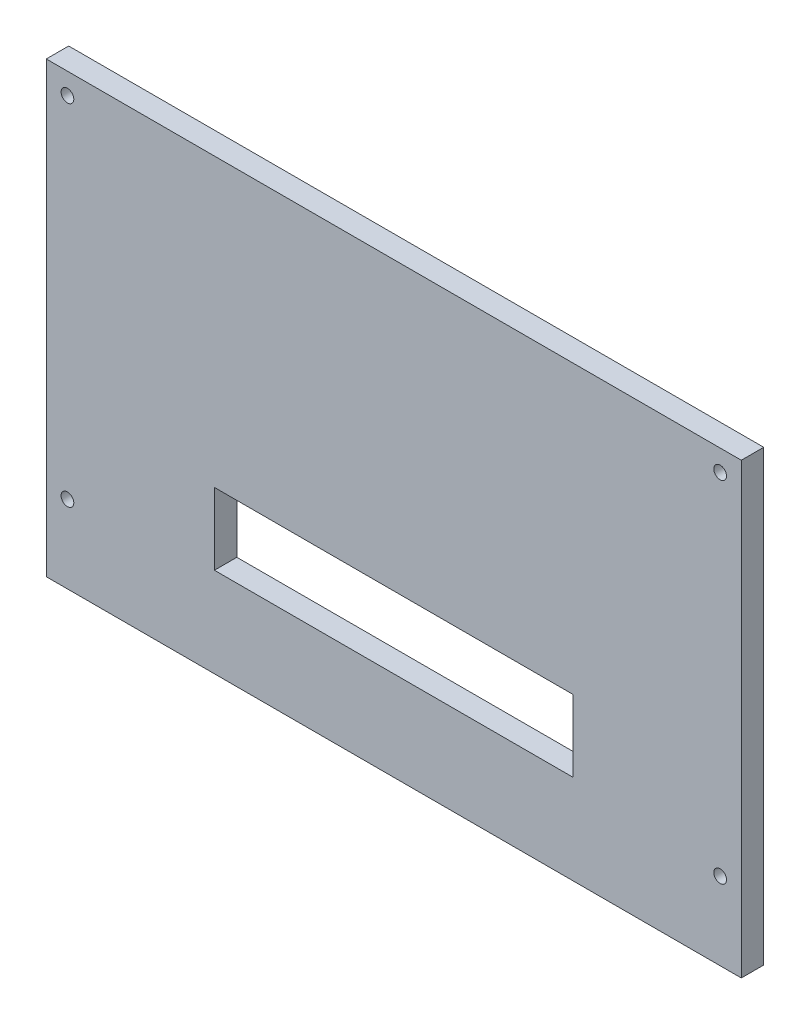
SolidWorks part; units mm, degrees
material "Acrylic (Medium-high impact)"
ref_plane "Front Plane" through (0, 0, 0) normal (0, 0, 1) x (1, 0, 0)
ref_plane "Top Plane" through (0, 0, 0) normal (0, 1, 0) x (1, 0, 0)
ref_plane "Right Plane" through (0, 0, 0) normal (1, 0, 0) x (0, 0, -1)
sketch "Sketch1" plane through (0, 0, 0) normal (0, 0, 1) x (1, 0, 0)
  line L1 (196.85, 127) -> (0, 127)
  line L2 (196.85, 127) -> (196.85, 0)
  line L3 (196.85, 0) -> (0, 0)
  line L4 (0, 127) -> (0, 0)
  line L5 (196.85, 127) -> (0, 0) construction
  line L6 (196.85, 0) -> (0, 127) construction
  point P0 (98.425, 63.5)
  dimension "D1" = 127
  dimension "D2" = 196.85
extrude "Boss-Extrude1" add sketch "Sketch1" along normal blind 6.35
hole_wizard "M3 Clearance Hole1" positions "Sketch2" profile "Sketch3" hole size "M3" standard "ANSI Metric" end condition through all
sketch "Sketch2" plane through (0, 0, 6.35) normal (0, 0, 1) x (1, 0, 0)
  line L0 (0, 127) -> (0, 0) construction
  line L1 (196.85, 127) -> (0, 127) construction
  line L2 (196.85, 0) -> (196.85, 127) construction
  line L3 (0, 0) -> (196.85, 0) construction
  point P0 (5.9944, 121.0056)
  point P2 (5.9944, 21.9964)
  point P4 (190.8556, 21.9964)
  point P6 (190.8556, 121.0056)
  dimension "D1" = 5.9944
  dimension "D2" = 5.9944
  dimension "D3" = 5.9944
  dimension "D4" = 21.9964
sketch "Sketch3" plane through (5.9944, 121.0056, 6.35) normal (1, 0, 0) x (0, -1, 0)
  line L0 (0, 0) -> (0, 6.35)
  line L1 (0, 6.35) -> (1.8, 6.35)
  line L2 (1.8, 6.35) -> (1.8, 0)
  line L5 (1.8, 0) -> (0, 0)
  line L11 (0, -6.35) -> (0, 107.95) construction
  dimension "Thru Hole Dia." = 3.6
  dimension "Thru Hole Depth" = 6.35
sketch "Sketch4" plane through (0, 0, 6.35) normal (0, 0, 1) x (1, 0, 0)
  line L0 (0, 127) -> (0, 0) construction
  line L1 (46.99, 107.95) -> (50.4952, 107.95)
  line L2 (46.99, 107.95) -> (46.99, 44.45)
  line L3 (46.99, 44.45) -> (50.4952, 44.45)
  line L4 (50.4952, 107.95) -> (50.4952, 44.45)
  line L5 (146.3548, 107.95) -> (149.86, 107.95)
  line L6 (146.3548, 107.95) -> (146.3548, 44.45)
  line L7 (146.3548, 44.45) -> (149.86, 44.45)
  line L8 (149.86, 107.95) -> (149.86, 44.45)
  line L9 (196.85, 0) -> (196.85, 127) construction
  line L10 (196.85, 127) -> (0, 127) construction
  dimension "D1" = 3.5052
  dimension "D2" = 63.5
  dimension "D3" = 46.99
  dimension "D4" = 46.99
  dimension "D5" = 19.05
extrude "Cut-Extrude1" [suppressed] cut sketch "Sketch4" against normal through all
sketch "Sketch5" plane through (0, 0, 6.35) normal (0, 0, 1) x (1, 0, 0)
  line L0 (0, 36.1092) -> (76.2, 25.4)
  line L1 (0, 127) -> (0, 0) construction
  line L2 (76.2, 25.4) -> (120.65, 25.4)
  line L3 (120.65, 25.4) -> (196.85, 36.1092)
  line L4 (196.85, 0) -> (196.85, 127) construction
  line L5 (196.85, 36.1092) -> (196.85, 0)
  line L6 (196.85, 0) -> (0, 0)
  line L7 (0, 0) -> (0, 36.1092)
  dimension "D1" = 8
  dimension "D2" = 8
  dimension "D3" = 76.2
  dimension "D4" = 76.2
  dimension "D5" = 25.4
extrude "Cut-Extrude2" [suppressed] cut sketch "Sketch5" against normal through all
sketch "Sketch7" plane through (0, 0, 6.35) normal (0, 0, 1) x (1, 0, 0)
  line L0 (0, 0) -> (196.85, 0) construction
  line L1 (47.625, 45.72) -> (149.225, 45.72)
  line L2 (47.625, 45.72) -> (47.625, 25.4)
  line L3 (47.625, 25.4) -> (149.225, 25.4)
  line L4 (149.225, 45.72) -> (149.225, 25.4)
  line L5 (47.625, 45.72) -> (149.225, 25.4) construction
  line L6 (47.625, 25.4) -> (149.225, 45.72) construction
  point P0 (98.425, 35.56)
  point P5 (98.425, 0)
  dimension "D1" = 20.32
  dimension "D2" = 101.6
  dimension "D3" = 25.4
extrude "tubingslot" cut sketch "Sketch7" against normal through all
